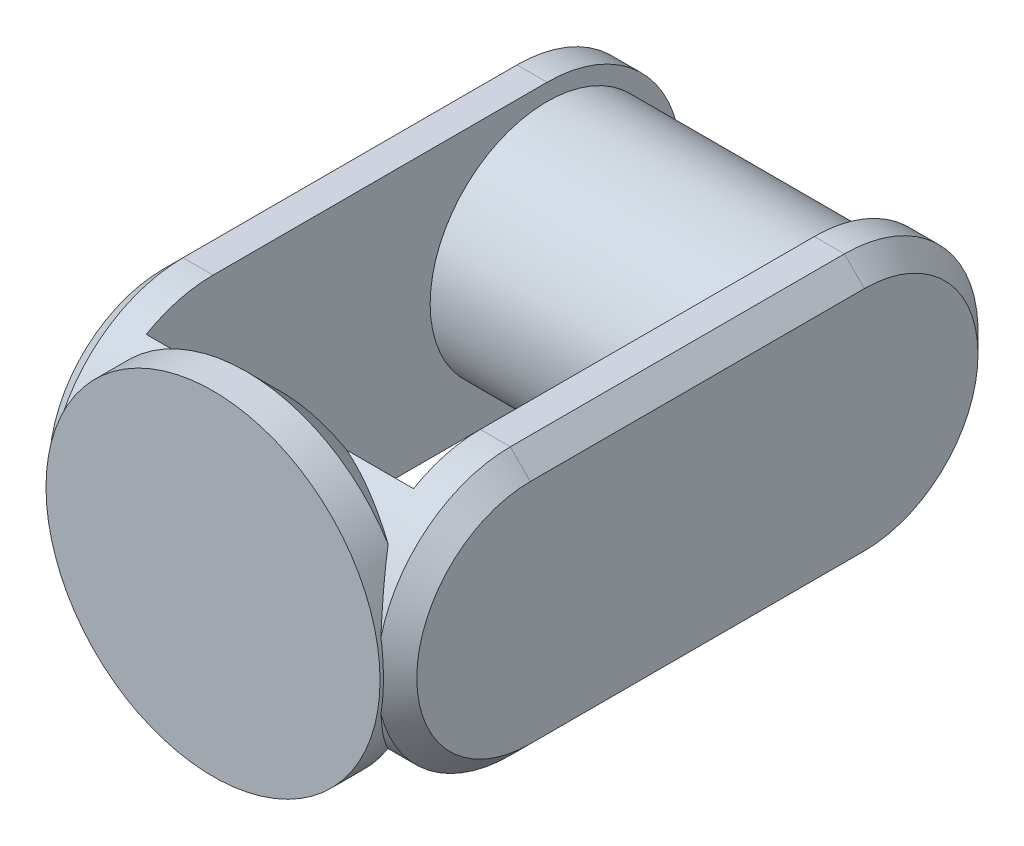
SolidWorks part; units mm, degrees
ref_plane "Front Plane" through (0, 0, 0) normal (0, 0, 1) x (1, 0, 0)
ref_plane "Top Plane" through (0, 0, 0) normal (0, 1, 0) x (1, 0, 0)
ref_plane "Right Plane" through (0, 0, 0) normal (1, 0, 0) x (0, 0, -1)
sketch "Sketch1" plane through (0, 0, 0) normal (0, 0, 1) x (1, 0, 0)
  circle A0 centre (0, 0) radius 25
  dimension "D1" = 50
extrude "Boss-Extrude1" add sketch "Sketch1" along normal blind 10
sketch "Sketch6" plane through (0, 0, 0) normal (1, 0, 0) x (0, 0, -1)
  line L0 (10, 0) -> (60, 0) construction
  line L1 (10, 20) -> (60, 20)
  line L2 (10, -20) -> (60, -20)
  line L3 (-10, 0) -> (4.7218, 0) construction
  line L5 (-10, 25) -> (-10, -25) construction
  arc A0 (10, 20) -> (10, -20) centre (10, 0) ccw
  arc A1 (60, -20) -> (60, 20) centre (60, 0) ccw
  point P3 (35, 0)
  point P12 (-10, 0)
  dimension "D2" = 20
  dimension "D1" = 50
extrude "Boss-Extrude3" add sketch "Sketch6" along normal mid plane 55
sketch "Sketch7" plane through (0, 20, 0) normal (0, 1, 0) x (1, 0, 0)
  line L1 (-20, 96.5335) -> (20, 96.5335)
  line L2 (-20, 96.5335) -> (-20, 0)
  line L3 (-20, 0) -> (20, 0)
  line L4 (20, 96.5335) -> (20, 0)
  point P4 (0, 0)
  dimension "D1" = 40
extrude "Cut-Extrude3" cut sketch "Sketch7" against normal blind 55
chamfer "Chamfer1" distance 3 angle 45 8 edges at (-27.5, -20, -35) (-27.5, 0, -80) (-27.5, 0, 10) (-27.5, 20, -35) (27.5, -20, -35) (27.5, 0, -80) (27.5, 0, 10) (27.5, 20, -35)
sketch "Sketch8" plane through (-20, 0, 0) normal (1, 0, 0) x (0, 0, -1)
  circle A0 centre (60, 0) radius 17.5
  dimension "D1" = 35
extrude "Boss-Extrude4" add sketch "Sketch8" along normal blind 40
chamfer "Chamfer2" distance 5 angle 45 2 edges at (0, -25, 0) (0, 25, 0)
